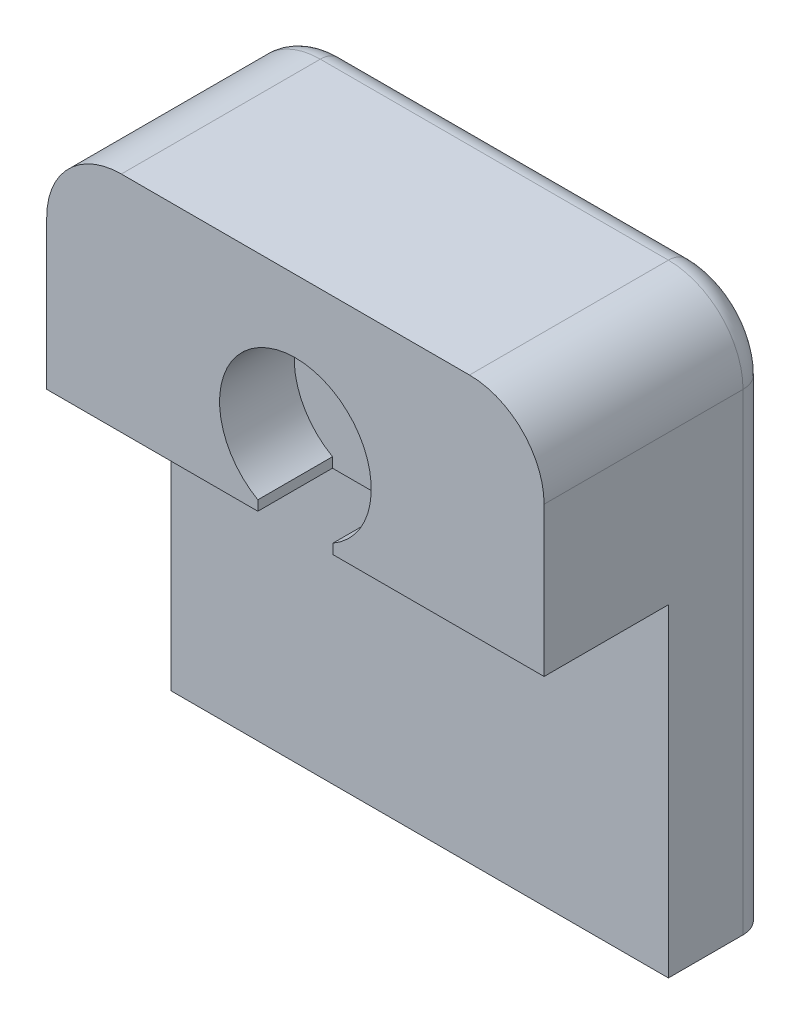
SolidWorks part; units mm, degrees
ref_plane "Front Plane" through (0, 0, 0) normal (0, 0, 1) x (1, 0, 0)
ref_plane "Top Plane" through (0, 0, 0) normal (0, 1, 0) x (1, 0, 0)
ref_plane "Right Plane" through (0, 0, 0) normal (1, 0, 0) x (0, 0, -1)
sketch "Sketch1" plane through (0, 0, 0) normal (0, 0, 1) x (1, 0, 0)
  line L1 (10, 4.5) -> (-10, 4.5)
  line L2 (10, 4.5) -> (10, -4.5)
  line L3 (10, -4.5) -> (-10, -4.5)
  line L4 (-10, 4.5) -> (-10, -4.5)
  line L5 (10, 4.5) -> (-10, -4.5) construction
  line L6 (10, -4.5) -> (-10, 4.5) construction
  point P0 (0, 0)
  dimension "D1" = 20
  dimension "D2" = 9
extrude "Boss-Extrude1" add sketch "Sketch1" along normal blind 13
sketch "Sketch2" plane through (0, 0, 13) normal (0, 0, 1) x (1, 0, 0)
  line L0 (0, -4.5) -> (0, -1.45) construction
  line L1 (-10, -4.5) -> (10, -4.5) construction
  line L2 (1.51, -4.5) -> (-1.51, -4.5)
  line L3 (-1.51, -4.5) -> (-1.51, -4.1)
  line L4 (1.51, -4.5) -> (1.51, -4.1)
  circle A0 centre (0, -1.45) radius 3.05
  point P9 (0, -4.5)
  line M4 (-10, -4.5) -> (10, -4.5)
  dimension "D1" = 3.05
  dimension "D2" = 3.02
extrude "Cut-Extrude1" cut sketch "Sketch2" against normal blind 3 contours A0 | A0 L2 L4 | A0 L3 M4 region at (1.1376, -4.3815, 13) region at (-1.1376, -4.3815, 13) region at (0, -1.45, 13)
fillet "Fillet1" radius 3 2 edges at (-10, 4.5, 6.5) (10, 4.5, 6.5)
sketch "Sketch3" plane through (0, -4.5, 0) normal (0, -1, 0) x (1, 0, 0)
  line L0 (-10, 13) -> (-10, 8)
  line L1 (-10, 13) -> (-10, 0) construction
  line L2 (-10, 8) -> (10, 8)
  line L3 (10, 13) -> (10, 0) construction
  line L4 (-10, 8) -> (-10, 4)
  line L5 (-10, 4) -> (10, 4)
  line M8 (-10, 13) -> (-10, 0)
  line M9 (-10, 0) -> (10, 0)
  line M10 (10, 0) -> (10, 13)
  dimension "D1" = 5
  dimension "D2" = 4
extrude "Cut-Extrude2" cut sketch "Sketch3" against normal blind 61 contours L5 M8 M9 M10 region at (0, -4.5, 2)
extrude "Boss-Extrude2" add sketch "Sketch3<3>" along normal blind 13 contours L5 L2 M8 M10 region at (0, -4.5, 6)
sketch "Sketch3<3>" plane through (0, -4.5, 0) normal (0, -1, 0) x (1, 0, 0) same geometry as "Sketch3"
fillet "Fillet4" radius 1 5 edges at (10, -8, 4) (9.1213, 3.6213, 4) (0, 4.5, 4) (-9.1213, 3.6213, 4) (-10, -8, 4)
